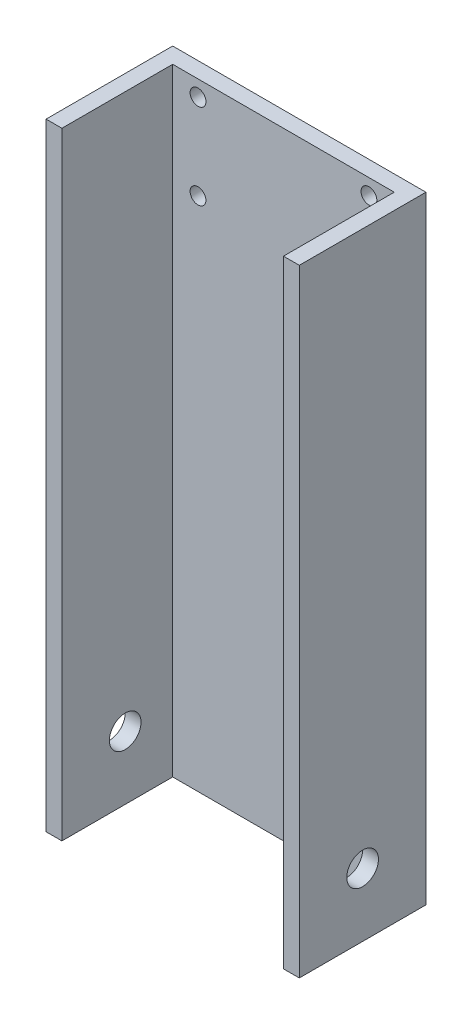
SolidWorks part; units mm, degrees
material "6061 Alloy"
ref_plane "Front Plane" through (0, 0, 0) normal (0, 0, 1) x (1, 0, 0)
ref_plane "Top Plane" through (0, 0, 0) normal (0, 1, 0) x (1, 0, 0)
ref_plane "Right Plane" through (0, 0, 0) normal (1, 0, 0) x (0, 0, -1)
sketch "Sketch1" plane through (0, 0, 0) normal (0, 1, 0) x (1, 0, 0)
  line L0 (0, 0) -> (25.4, 0) construction
  line L1 (0, 0) -> (0, 25.4) construction
  line L2 (25.4, 0) -> (25.4, 25.4)
  line L3 (-25.4, 0) -> (-25.4, 25.4)
  line L4 (25.4, 25.4) -> (-25.4, 25.4)
  line L5 (22.225, 0) -> (22.225, 22.225)
  line L6 (22.225, 22.225) -> (-22.225, 22.225)
  line L7 (-22.225, 0) -> (-22.225, 22.225)
  line L8 (25.4, 0) -> (22.225, 0)
  line L9 (-25.4, 0) -> (-22.225, 0)
  dimension "D1" = 25.4
  dimension "D2" = 25.4
  dimension "D3" = 3.175
extrude "Boss-Extrude1" add sketch "Sketch1" along normal blind 123.825
sketch "Sketch2" plane through (25.4, 0, 0) normal (1, 0, 0) x (0, 0, -1)
  line L0 (12.7, 0) -> (12.7, 12.7) construction
  line L1 (0, 0) -> (25.4, 0) construction
  circle A0 centre (12.7, 12.7) radius 3.175
  dimension "D1" = 12.7
extrude "Cut-Extrude1" cut sketch "Sketch2" against normal blind 70
sketch "Sketch3" plane through (0, 0, -25.4) normal (0, 0, -1) x (-1, 0, 0)
  line L0 (0, 123.825) -> (0, 120.65) construction
  line L1 (-25.4, 123.825) -> (25.4, 123.825) construction
  line L2 (0, 120.65) -> (17.145, 120.65) construction
  line L3 (17.145, 120.65) -> (17.145, 103.505) construction
  circle A0 centre (17.145, 103.505) radius 1.5875
  circle A1 centre (17.145, 120.65) radius 1.5875
  circle A2 centre (-17.145, 103.505) radius 1.5875
  circle A3 centre (-17.145, 120.65) radius 1.5875
  dimension "D1" = 3.175
  dimension "D2" = 17.145
extrude "Cut-Extrude2" cut sketch "Sketch3" against normal blind 70
